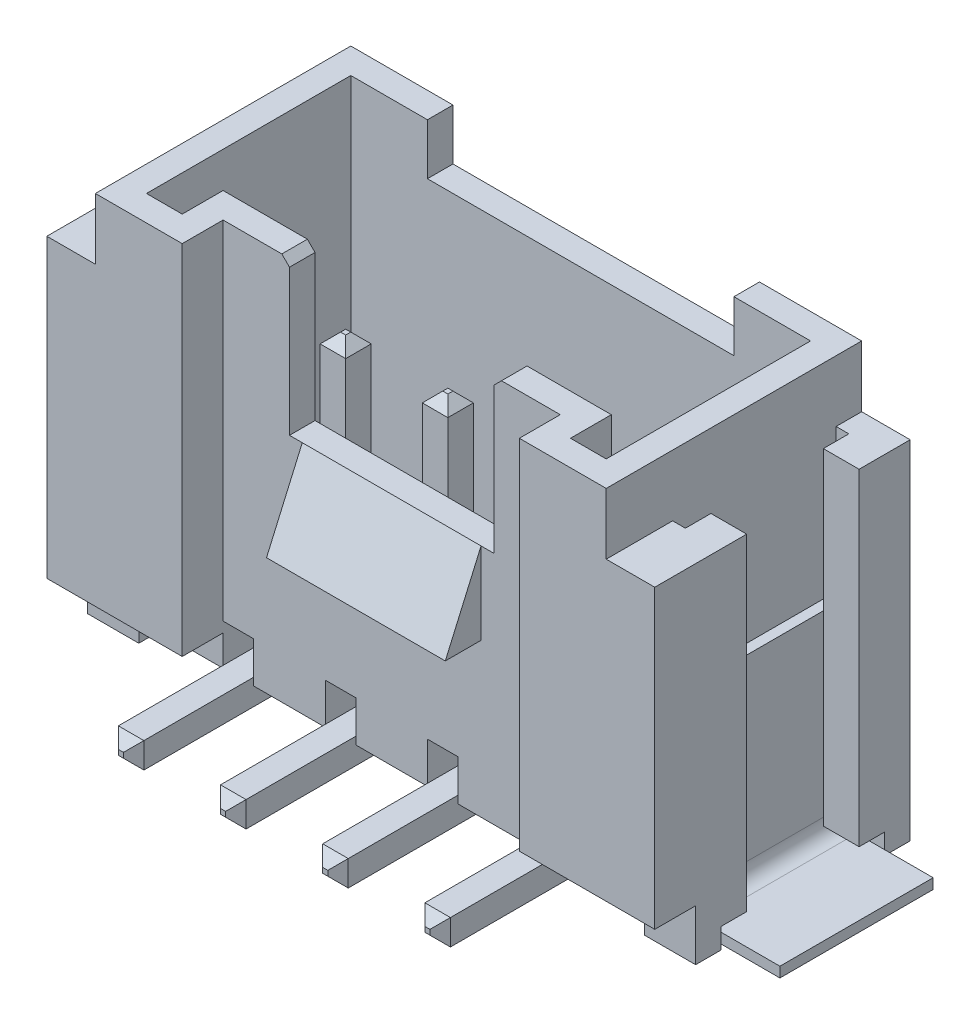
SolidWorks part; units mm, degrees
material "ABS"
ref_plane "Plan de face" through (0, 0, 0) normal (0, 0, 1) x (1, 0, 0)
ref_plane "Plan de dessus" through (0, 0, 0) normal (0, 1, 0) x (1, 0, 0)
ref_plane "Plan de droite" through (0, 0, 0) normal (1, 0, 0) x (0, 0, -1)
sketch "Esquisse1" plane through (0, 0, 0) normal (0, 1, 0) x (1, 0, 0)
  line L1 (-5, 0) -> (5, 0)
  line L2 (-5, 0) -> (-5, 5)
  line L3 (-5, 5) -> (5, 5)
  line L4 (5, 0) -> (5, 5)
  dimension "D1" = 10
  dimension "D2" = 5
extrude "Boss.-Extru.1" add sketch "Esquisse1" along normal blind 8
sketch "Esquisse2" plane through (0, 8, 0) normal (0, 1, 0) x (1, 0, 0)
  line L0 (-5, 0) -> (5, 0) construction
  line L1 (-3.3, -0.8) -> (3.3, -0.8)
  line L2 (-3.3, -0.8) -> (-3.3, 0.8)
  line L3 (-3.3, 0.8) -> (3.3, 0.8)
  line L4 (3.3, -0.8) -> (3.3, 0.8)
  line L5 (-3.3, -0.8) -> (3.3, 0.8) construction
  line L6 (-3.3, 0.8) -> (3.3, -0.8) construction
  line L7 (5, 0) -> (5, 5) construction
  point P0 (0, 0)
  dimension "D1" = 0.8
  dimension "D2" = 1.7
extrude "Enlèv. mat.-Extru.1" cut sketch "Esquisse2" against normal through all
sketch "Esquisse4" plane through (0, 8, 0) normal (0, 1, 0) x (1, 0, 0)
  line L16 (-3.8, 1.3) -> (3.8, 1.3)
  line L17 (3.8, 1.3) -> (3.8, 0.5)
  line L18 (3.8, 0.5) -> (4.5, 0.5)
  line L19 (4.5, 0.5) -> (4.5, 4.5)
  line L20 (4.5, 4.5) -> (-4.5, 4.5)
  line L21 (-4.5, 4.5) -> (-4.5, 0.5)
  line L22 (-4.5, 0.5) -> (-3.8, 0.5)
  line L23 (-3.8, 0.5) -> (-3.8, 1.3)
  line L24 (-3.8, 1.3) -> (3.8, 1.3)
  line L25 (3.8, 1.3) -> (3.8, 0.5)
  line L26 (3.8, 0.5) -> (4.5, 0.5)
  line L27 (4.5, 0.5) -> (4.5, 4.5)
  line L28 (4.5, 4.5) -> (-4.5, 4.5)
  line L29 (-4.5, 4.5) -> (-4.5, 0.5)
  line L30 (-4.5, 0.5) -> (-3.8, 0.5)
  line L31 (-3.8, 0.5) -> (-3.8, 1.3)
  dimension "D1" = 0.5
extrude "Enlèv. mat.-Extru.2" cut sketch "Esquisse4" against normal blind 6.5
sketch "Esquisse17" plane through (0, 8, 0) normal (0, 1, 0) x (1, 0, 0)
  line L0 (5, 0) -> (5, 5) construction
  line L1 (5, 5) -> (5.95, 5)
  line L2 (5, 5) -> (5, 0)
  line L3 (5, 0) -> (5.95, 0)
  line L4 (5.95, 5) -> (5.95, 0)
  line L5 (5, 5) -> (-5, 5) construction
  line L6 (5, 4.5) -> (5.25, 4.5)
  line L7 (5.25, 4.5) -> (5.25, 4)
  line L8 (5.25, 4) -> (5.95, 4)
  line L9 (5, 2.9) -> (5.95, 2.9) construction
  line L10 (5.25, 1.8) -> (5.95, 1.8)
  line L11 (5.25, 1.3) -> (5.25, 1.8)
  line L12 (5, 1.3) -> (5.25, 1.3)
  line L13 (5.95, 4) -> (5.95, 1.8)
  line L14 (5, 1.3) -> (5, 4.5)
  line M12 (5, 0) -> (5, 5)
  dimension "D1" = 5.95
  dimension "D2" = 2.2
  dimension "D3" = 3.2
  dimension "D4" = 1
  dimension "D5" = 0.25
extrude "Boss.-Extru.3" add sketch "Esquisse17" against normal up to surface (8 mm away) from offset 1.2 contours L7 L8 L4 L1 L2 L6 | L12 L3 L4 L10 L11 M12 region at (5.528, 8, -4.5379) region at (5.5026, 8, -0.8487) up to face at (0, 0, -1.45) offset against normal yes
mirror "Symétrie3" about plane through (0, 0, 0) normal (1, 0, 0) of "Boss.-Extru.3"
sketch "Esquisse5" plane through (0, 8, 0) normal (0, 1, 0) x (1, 0, 0)
  line L0 (4.5, 4.5) -> (-4.5, 4.5) construction
  line L1 (-3, 4) -> (3, 4)
  line L2 (-3, 4) -> (-3, 5)
  line L3 (-3, 5) -> (3, 5)
  line L4 (3, 4) -> (3, 5)
  line L5 (-3, 4) -> (3, 5) construction
  line L6 (-3, 5) -> (3, 4) construction
  line L7 (5, 5) -> (-5, 5) construction
  line L8 (5, 0) -> (5, 5) construction
  point P0 (0, 4.5)
  dimension "D1" = 2
extrude "Enlèv. mat.-Extru.3" cut sketch "Esquisse5" against normal blind 1
sketch "Esquisse6" plane through (0, 8, 0) normal (0, 1, 0) x (1, 0, 0)
  line L0 (3.3, 0.8) -> (-3.3, 0.8) construction
  line L1 (-2, 0.3) -> (2, 0.3)
  line L2 (-2, 0.3) -> (-2, 1.3)
  line L3 (-2, 1.3) -> (2, 1.3)
  line L4 (2, 0.3) -> (2, 1.3)
  line L5 (-2, 0.3) -> (2, 1.3) construction
  line L6 (-2, 1.3) -> (2, 0.3) construction
  line L7 (-3.8, 1.3) -> (3.8, 1.3) construction
  line L8 (5, 0) -> (5, 5) construction
  point P0 (0, 0.8)
  dimension "D1" = 3
extrude "Enlèv. mat.-Extru.4" cut sketch "Esquisse6" against normal blind 3
sketch "Esquisse7" plane through (5.95, 0, 0) normal (1, 0, 0) x (0, 0, -1)
  line L0 (0, 0) -> (0, 6.8) construction
  line L1 (0, 1) -> (0.8, 1)
  line L2 (0, 1) -> (0, 0)
  line L3 (0, 0) -> (0.8, 0)
  line L4 (0.8, 1) -> (0.8, 0)
  line L5 (1.8, 0) -> (0, 0) construction
  dimension "D1" = 1
  dimension "D2" = 0.8
extrude "Enlèv. mat.-Extru.5" cut sketch "Esquisse7" against normal through all
sketch "Esquisse11" plane through (0, 0, 0) normal (1, 0, 0) x (0, 0, -1)
  line L0 (0.8, 5) -> (0.1, 3.4)
  line L1 (0.8, 5) -> (0.8, 8) construction
  line L2 (1.3, 5) -> (0.8, 5) construction
  line L3 (0.1, 3.4) -> (0.8, 3.4)
  line L4 (0.8, 1) -> (0.8, 8) construction
  line L5 (0.8, 3.4) -> (0.8, 5)
  dimension "D1" = 0.7
  dimension "D2" = 1.6
extrude "Boss.-Extru.2" add sketch "Esquisse11" along normal mid plane 3.5
sketch "Esquisse18" plane through (0, 0, -0.8) normal (0, 0, 1) x (1, 0, 0)
  line L0 (5.95, 0) -> (-5.95, 0) construction
  line L1 (-4.95, -0.4) -> (4.95, -0.4)
  line L2 (-4.95, -0.4) -> (-4.95, 0.4)
  line L3 (-4.95, 0.4) -> (4.95, 0.4)
  line L4 (4.95, -0.4) -> (4.95, 0.4)
  line L5 (-4.95, -0.4) -> (4.95, 0.4) construction
  line L6 (-4.95, 0.4) -> (4.95, -0.4) construction
  line L7 (5.95, 0) -> (5.95, 1) construction
  line L9 (2.7, -0.4) -> (3.3, -0.4)
  line L10 (2.7, -0.4) -> (2.7, 1.2)
  line L11 (2.7, 1.2) -> (3.3, 1.2)
  line L12 (3.3, -0.4) -> (3.3, 1.2)
  line L13 (2.7, -0.4) -> (3.3, 1.2) construction
  line L14 (2.7, 1.2) -> (3.3, -0.4) construction
  line L15 (0.7, -0.4) -> (1.3, -0.4)
  line L16 (0.7, -0.4) -> (0.7, 1.2)
  line L17 (0.7, 1.2) -> (1.3, 1.2)
  line L18 (1.3, -0.4) -> (1.3, 1.2)
  line L19 (0.7, -0.4) -> (1.3, 1.2) construction
  line L20 (0.7, 1.2) -> (1.3, -0.4) construction
  line L21 (-1.3, -0.4) -> (-0.7, -0.4)
  line L22 (-1.3, -0.4) -> (-1.3, 1.2)
  line L23 (-1.3, 1.2) -> (-0.7, 1.2)
  line L24 (-0.7, -0.4) -> (-0.7, 1.2)
  line L25 (-1.3, -0.4) -> (-0.7, 1.2) construction
  line L26 (-1.3, 1.2) -> (-0.7, -0.4) construction
  line L27 (-3.3, -0.4) -> (-2.7, -0.4)
  line L28 (-3.3, -0.4) -> (-3.3, 1.2)
  line L29 (-3.3, 1.2) -> (-2.7, 1.2)
  line L30 (-2.7, -0.4) -> (-2.7, 1.2)
  line L31 (-3.3, -0.4) -> (-2.7, 1.2) construction
  line L32 (-3.3, 1.2) -> (-2.7, -0.4) construction
  point P0 (0, 0)
  point P10 (3, 0.4)
  point P15 (1, 0.4)
  point P20 (-1, 0.4)
  point P25 (-3, 0.4)
  line M7 (-3.3, 8) -> (-3.3, 1)
  line M13 (3.3, 1) -> (3.3, 8)
  dimension "D1" = 0.4
  dimension "D2" = 1
  dimension "D3" = 2
  dimension "D4" = 1
  dimension "D5" = 2
  dimension "D6" = 2
  dimension "D7" = 1.2
  dimension "D8" = 0.6
extrude "Enlèv. mat.-Extru.6" cut sketch "Esquisse18" against normal through all contours L3 L30 L29 L28 M7 | L3 L24 L23 L22 | L3 L18 L17 L16 | L3 L12 L11 L10 M13 | L3 L4 L1 L2 region at (-3, 0.8, -0.8) region at (-1, 0.8, -0.8) region at (1, 0.8, -0.8) region at (3, 0.8, -0.8)
sketch "Esquisse20" plane through (5.25, 0, 0) normal (-1, 0, 0) x (0, 0, 1)
  line L0 (-4.5, 0) -> (-4, 0) construction
  line L1 (-4.5, 0) -> (-1.3, 0)
  line L2 (-4.5, 0) -> (-4.5, 0.4)
  line L3 (-4.5, 0.4) -> (-1.3, 0.4)
  line L4 (-1.3, 0) -> (-1.3, 0.4)
  line L5 (-1.3, 0) -> (-1.3, 6.8) construction
  line L6 (-4.5, 0.4) -> (-1.3, 0.4) construction
extrude "Enlèv. mat.-Extru.7" cut sketch "Esquisse20" against normal through all and the other way through all
chamfer "Chanfrein1" distance 0.15 angle 45 2 edges at (2, 8, -1.05) (-2, 8, -1.05)
ref_plane "Plan1" through (3, 0, 0) normal (1, 0, 0) x (0, 0, -1)
sketch "Esquisse21" plane through (3, 0, 0) normal (1, 0, 0) x (0, 0, -1)
  line L0 (2.9, 5.2) -> (2.9, 0.75)
  line L1 (2.4, 0.25) -> (-1.5, 0.25)
  line L2 (4.5, 8) -> (0.5, 8) construction
  line L3 (1.3, 0) -> (0.8, 0) construction
  line L4 (4.5, 1.5) -> (4.5, 8) construction
  arc A0 (2.9, 0.75) -> (2.4, 0.25) centre (2.4, 0.75) cw
  dimension "D3" = 0.5
  dimension "D1" = 6.5
  dimension "D2" = 2.8
  dimension "D4" = 0.25
  dimension "D5" = 1.6
extrude "Extru.-Mince1" add sketch "Esquisse21" along normal mid plane 0.5 separate body thin thin type mid plane wall 0.5
chamfer "Chanfrein2" distance 0.2 angle 45 8 edges at (3, 0.5, 1.5) (3.25, 0.25, 1.5) (3, 0, 1.5) (2.75, 0.25, 1.5) (3, 5.2, -3.15) (3.25, 5.2, -2.9) (3, 5.2, -2.65) (2.75, 5.2, -2.9)
pattern_linear "Répétition linéaire1" count 4 spacing 2 along (1, 0, 0) of "Extru.-Mince1", "Chanfrein2"
sketch "Esquisse22" plane through (0, 0, -1.3) normal (0, 0, -1) x (-1, 0, 0)
  line L0 (-5, 4) -> (-5, 0.5)
  line L1 (-5, 0.4) -> (-5, 6.8) construction
  line L2 (-5.5, 0) -> (-7, 0)
  line L4 (-5, 8) -> (-3, 8) construction
  arc A0 (-5, 0.5) -> (-5.5, 0) centre (-5.5, 0.5) cw
  point P13 (-4.95, 0)
  dimension "D3" = 0.5
  dimension "D1" = 1.5
  dimension "D2" = 4
extrude "Extru.-Mince2" add sketch "Esquisse22" along normal blind 3 from offset 0.1 separate body thin thin type one direction wall 0.2
mirror "Symétrie4" about plane through (0, 0, 0) normal (1, 0, 0) of bodies 122
